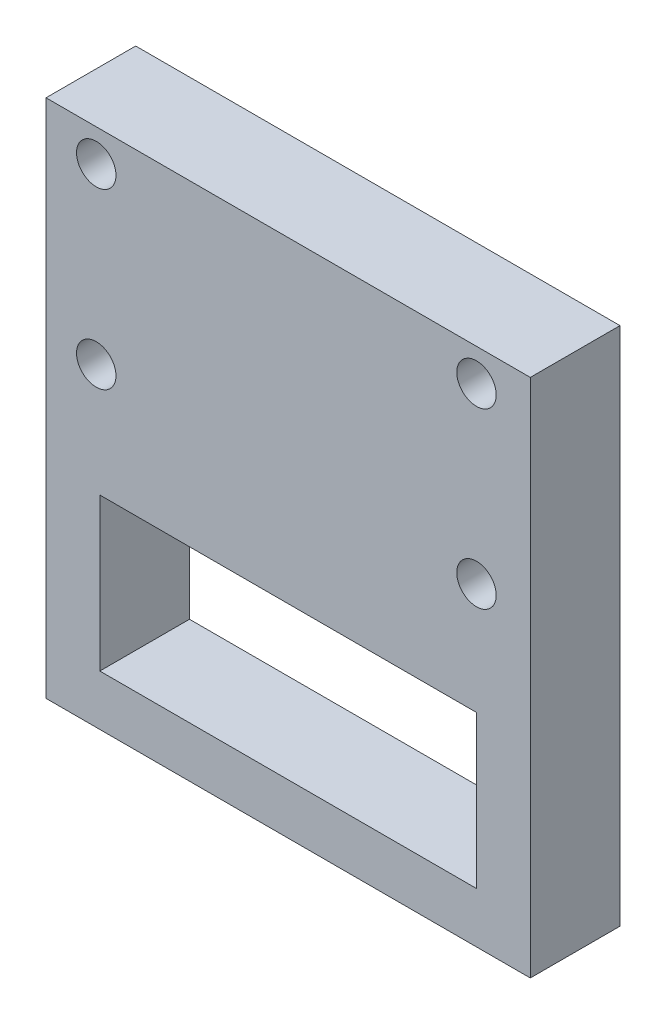
SolidWorks part; units mm, degrees
ref_plane "Front Plane" through (0, 0, 0) normal (0, 0, 1) x (1, 0, 0)
ref_plane "Top Plane" through (0, 0, 0) normal (0, 1, 0) x (1, 0, 0)
ref_plane "Right Plane" through (0, 0, 0) normal (1, 0, 0) x (0, 0, -1)
sketch "Sketch1" plane through (0, 0, 0) normal (0, 0, 1) x (1, 0, 0)
  line L1 (-13.5, 14.5) -> (13.5, 14.5)
  line L2 (-13.5, 14.5) -> (-13.5, -14.5)
  line L3 (-13.5, -14.5) -> (13.5, -14.5)
  line L4 (13.5, 14.5) -> (13.5, -14.5)
  line L5 (-13.5, 14.5) -> (13.5, -14.5) construction
  line L6 (-13.5, -14.5) -> (13.5, 14.5) construction
  point P0 (0, 0)
  dimension "D1" = 27
  dimension "D2" = 29
extrude "Boss-Extrude1" add sketch "Sketch1" along normal blind 5
sketch "Sketch2" plane through (0, -14.5, 0) normal (0, -1, 0) x (1, 0, 0)
  line L0 (-13.5, 2.5) -> (13.5, 2.5) construction
  line L1 (-13.5, 5) -> (-13.5, 0) construction
  line L2 (13.5, 5) -> (13.5, 0) construction
  circle A0 centre (-7, 2.5) radius 1.25
  circle A1 centre (0, 2.5) radius 1.25
  circle A2 centre (7, 2.5) radius 1.25
  point P13 (13.5, 2.5)
  dimension "D1" = 2.5
  dimension "D2" = 7
  dimension "D3" = 7
extrude "Cut-Extrude1" cut sketch "Sketch2" against normal blind 2.18
sketch "Sketch3" plane through (0, 0, 5) normal (0, 0, 1) x (1, 0, 0)
  line L0 (0, 14.5) -> (0, -14.5) construction
  line L1 (13.5, 14.5) -> (-13.5, 14.5) construction
  line L2 (-13.5, -14.5) -> (13.5, -14.5) construction
  line L3 (-13.5, 0) -> (13.5, 0) construction
  line L4 (-13.5, 14.5) -> (-13.5, -14.5) construction
  line L5 (13.5, -14.5) -> (13.5, 14.5) construction
  line L6 (-12.5, 15.7476) -> (12.5, 15.7476) construction
  line L7 (-13.5, -9.36) -> (13.5, -9.36) construction
  line L8 (-5.4, 5.4) -> (5.4, 5.4) construction
  line L9 (-5.4, 5.4) -> (-5.4, -5.4) construction
  line L10 (-5.4, -5.4) -> (5.4, -5.4) construction
  line L11 (5.4, 5.4) -> (5.4, -5.4) construction
  line L12 (-5.4, 5.4) -> (5.4, -5.4) construction
  line L13 (-5.4, -5.4) -> (5.4, 5.4) construction
  line L14 (-10.7, 5.4) -> (-10.7, 0.65) construction
  circle A0 centre (-10.7, 12.7) radius 1.1
  circle A1 centre (10.5, 12.7) radius 1.1
  circle A2 centre (-10.7, 12.7) radius 2.375 construction
  circle A3 centre (-10.7, 3.025) radius 2.375 construction
  circle A4 centre (-10.7, 3.025) radius 1.1
  circle A5 centre (10.5, 3.025) radius 1.1
  circle A6 centre (0, 0) radius 3.475 construction
  point P22 (0, 15.7476)
  point P24 (0, 0)
  dimension "D1" = 2.2
  dimension "D5" = 4.75
  dimension "D6" = 4.75
  dimension "D8" = 2.2
  dimension "D13" = 6.95
  dimension "D7" = 7.3
  dimension "D2" = 1.8
  dimension "D3" = 1.8
  dimension "D4" = 2
  dimension "D9" = 10.8
  dimension "D10" = 25
  dimension "D11" = 10.8
  dimension "D12" = 7.3
  dimension "D14" = 23.86
  dimension "D15" = 14.5
  dimension "D16" = 21.2
  dimension "D17" = 9.675
  dimension "D18" = 9.36
  dimension "D19" = 14.5
extrude "Cut-Extrude2" cut sketch "Sketch3" against normal blind 10
sketch "Sketch4" plane through (0, 0, 5) normal (0, 0, 1) x (1, 0, 0)
  line L0 (0, 14.5) -> (0, -14.5) construction
  line L1 (13.5, 14.5) -> (-13.5, 14.5) construction
  line L2 (-13.5, -14.5) -> (13.5, -14.5) construction
  line L4 (-10.5, -3.1791) -> (10.5, -3.1791)
  line L5 (-10.5, -3.1791) -> (-10.5, -11.6791)
  line L6 (-10.5, -11.6791) -> (10.5, -11.6791)
  line L7 (10.5, -3.1791) -> (10.5, -11.6791)
  line L8 (-10.5, -3.1791) -> (10.5, -11.6791) construction
  line L9 (-10.5, -11.6791) -> (10.5, -3.1791) construction
  point P6 (0, -7.4291)
  dimension "D1" = 21
  dimension "D2" = 8.5
extrude "Cut-Extrude3" cut sketch "Sketch4" against normal blind 10
